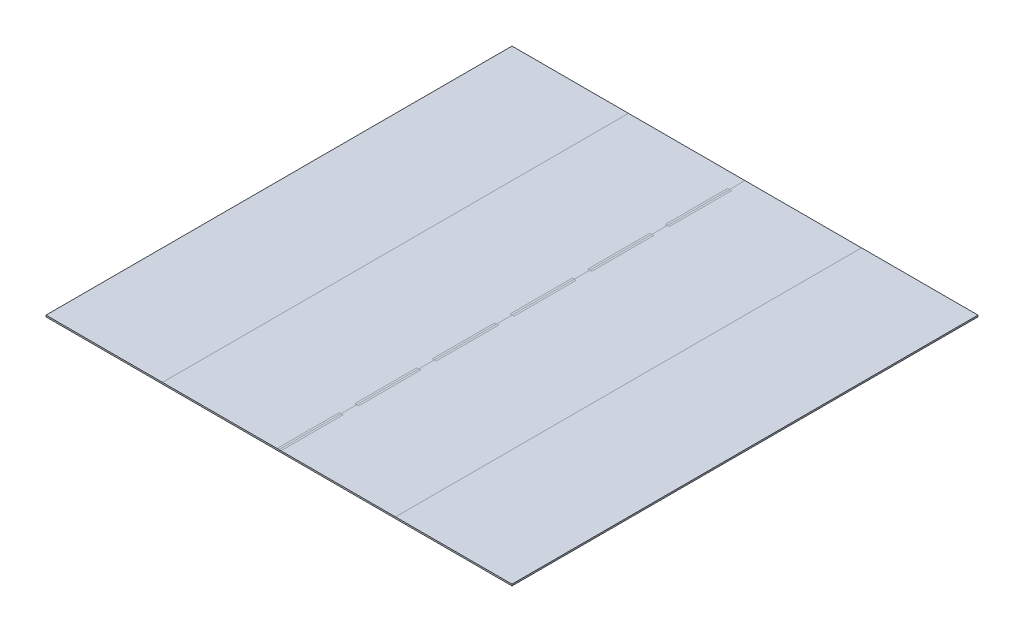
SolidWorks part; units mm, degrees
ref_plane "Front Plane" through (0, 0, 0) normal (0, 0, 1) x (1, 0, 0)
ref_plane "Top Plane" through (0, 0, 0) normal (0, 1, 0) x (1, 0, 0)
ref_plane "Right Plane" through (0, 0, 0) normal (1, 0, 0) x (0, 0, -1)
sketch "Sketch8" plane through (0, 0, 0) normal (0, 1, 0) x (1, 0, 0)
  line L1 (-296.5616, -440.5444) -> (1203.4384, -440.5444)
  line L2 (-296.5616, -440.5444) -> (-296.5616, 1059.4556)
  line L3 (-296.5616, 1059.4556) -> (1203.4384, 1059.4556)
  line L4 (1203.4384, -440.5444) -> (1203.4384, 1059.4556)
  line L5 (78.4384, 1059.4556) -> (828.4384, 1059.4556)
  line L6 (78.4384, 1059.4556) -> (78.4384, -440.5444)
  line L7 (78.4384, -440.5444) -> (828.4384, -440.5444)
  line L8 (828.4384, 1059.4556) -> (828.4384, -440.5444)
  dimension "D1" = 1500
  dimension "D2" = 1500
  dimension "D3" = 750
  dimension "D4" = 1500
extrude "Boss-Extrude18" add sketch "Sketch8" along normal blind 5 contours L8 L3 L6 L1 | L3 L8 L1 L4 | L6 L3 L2 L1 region at (-109.0616, 0, -309.4556) region at (453.4384, 0, -309.4556) region at (1015.9384, 0, -309.4556)
split line "Split Line26"
sketch "Sketch8<3>" plane through (0, 0, 0) normal (0, 1, 0) x (1, 0, 0) same geometry as "Sketch8"
sketch "Sketch9" plane through (0, 5, 0) normal (0, 1, 0) x (1, 0, 0)
  line L0 (78.4384, -440.5444) -> (828.4384, -440.5444) construction
  line L1 (78.4384, 1059.4556) -> (453.4384, 1059.4556)
  line L2 (78.4384, 1059.4556) -> (78.4384, -440.5444)
  line L3 (78.4384, -440.5444) -> (453.4384, -440.5444)
  line L4 (453.4384, 1059.4556) -> (453.4384, -440.5444)
  line L5 (447.1884, 9.4556) -> (447.1884, -190.5444)
  line L6 (447.1884, -240.5444) -> (459.6884, -240.5444)
  line L7 (447.1884, -240.5444) -> (447.1884, -440.5444)
  line L8 (447.1884, -440.5444) -> (459.6884, -440.5444)
  line L9 (459.6884, -240.5444) -> (459.6884, -440.5444)
  line L10 (447.1884, 9.4556) -> (459.6884, 9.4556)
  line L11 (459.6884, 9.4556) -> (459.6884, -190.5444)
  line L12 (447.1884, -190.5444) -> (459.6884, -190.5444)
  line L13 (447.1884, 259.4556) -> (447.1884, 59.4556)
  line L14 (447.1884, 259.4556) -> (459.6884, 259.4556)
  line L15 (459.6884, 259.4556) -> (459.6884, 59.4556)
  line L16 (447.1884, 59.4556) -> (459.6884, 59.4556)
  line L17 (447.1884, 509.4556) -> (447.1884, 309.4556)
  line L18 (447.1884, 509.4556) -> (459.6884, 509.4556)
  line L19 (459.6884, 509.4556) -> (459.6884, 309.4556)
  line L20 (447.1884, 309.4556) -> (459.6884, 309.4556)
  line L21 (447.1884, 759.4556) -> (447.1884, 559.4556)
  line L22 (447.1884, 759.4556) -> (459.6884, 759.4556)
  line L23 (459.6884, 759.4556) -> (459.6884, 559.4556)
  line L24 (447.1884, 559.4556) -> (459.6884, 559.4556)
  line L25 (447.1884, 1009.4556) -> (447.1884, 809.4556)
  line L26 (447.1884, 1009.4556) -> (459.6884, 1009.4556)
  line L27 (459.6884, 1009.4556) -> (459.6884, 809.4556)
  line L28 (447.1884, 809.4556) -> (459.6884, 809.4556)
  point P11 (453.4384, -240.5444)
  dimension "D1" = 12.5
  dimension "D2" = 200
  dimension "D3" = 6
split line "Split Line27"
equation "\"Scale\"= 8"
equation "\"Tile Size\"= \"Road Size\" * 2"
equation "\"Road Size\"= \"Real Lane Size\" * 2 / \"Scale\""
equation "\"Real Lane Size\"= 3m"
